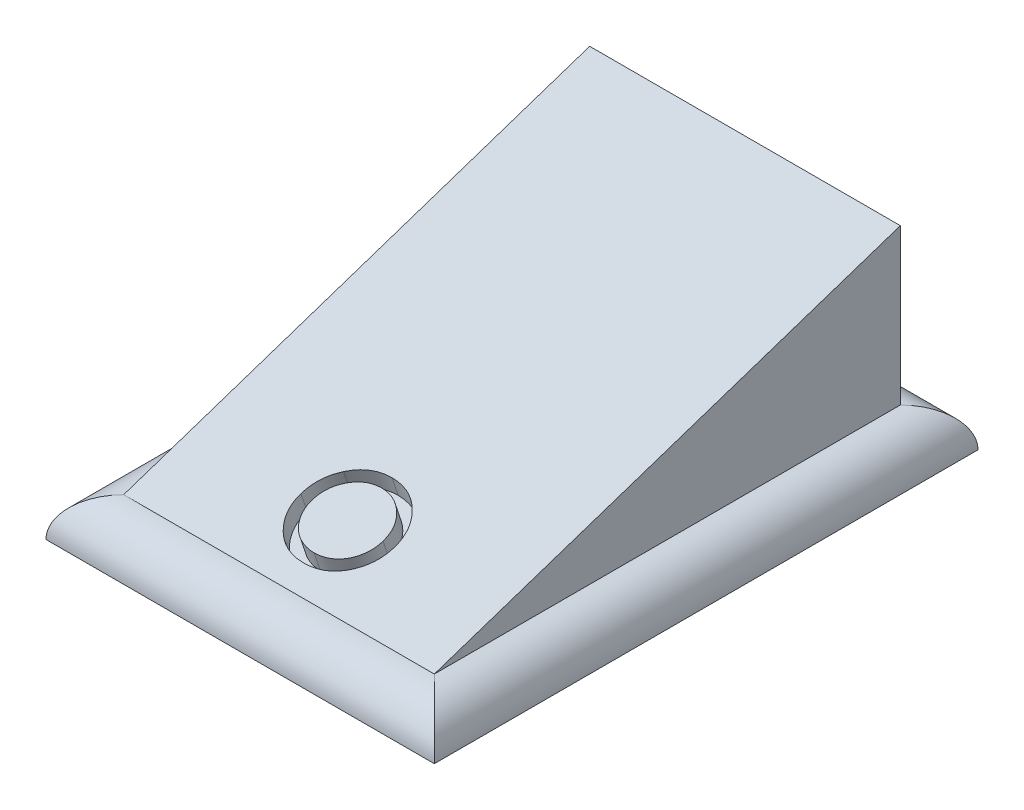
SolidWorks part; units mm, degrees
ref_plane "Front Plane" through (0, 0, 0) normal (0, 0, 1) x (1, 0, 0)
ref_plane "Top Plane" through (0, 0, 0) normal (0, 1, 0) x (1, 0, 0)
ref_plane "Right Plane" through (0, 0, 0) normal (1, 0, 0) x (0, 0, -1)
sketch "Sketch1" plane through (0, 0, 0) normal (0, 1, 0) x (1, 0, 0)
  line L1 (0, 0) -> (10, 0)
  line L2 (0, 0) -> (0, 14)
  line L3 (0, 14) -> (10, 14)
  line L4 (10, 0) -> (10, 14)
  dimension "D1" = 10
  dimension "D2" = 14
extrude "Boss-Extrude1" add sketch "Sketch1" along normal blind 1
sketch "Sketch2" plane through (0, 1, 0) normal (0, 1, 0) x (1, 0, 0)
  line L0 (0, 0) -> (10, 0) construction
  line L1 (1, 13) -> (9, 13)
  line L2 (1, 13) -> (1, 1)
  line L3 (1, 1) -> (9, 1)
  line L4 (9, 13) -> (9, 1)
  line L5 (0, 14) -> (0, 0) construction
  dimension "D1" = 8
  dimension "D2" = 12
  dimension "D3" = 1
  dimension "D4" = 1
extrude "Boss-Extrude2" add sketch "Sketch2" along normal blind 4
sketch "Sketch3" plane through (1, 0, 0) normal (-1, 0, 0) x (0, 0, 1)
  line L0 (-13, 5) -> (-1, 1)
  line L1 (-1, 1) -> (-1, 5)
  line L2 (-1, 5) -> (-13, 5)
extrude "Cut-Extrude1" cut sketch "Sketch3" against normal blind 8
sketch "Sketch4" plane through (0, 0.6, 0.2) normal (0, 0.9487, 0.3162) x (1, 0, 0)
  text T0 "o"
extrude "Cut-Extrude2" cut sketch "Sketch4" against normal blind 0.5
fillet "Fillet1" radius 1 4 edges at (5, 1, -14) (10, 1, -7) (5, 1, 0) (0, 1, -7)
